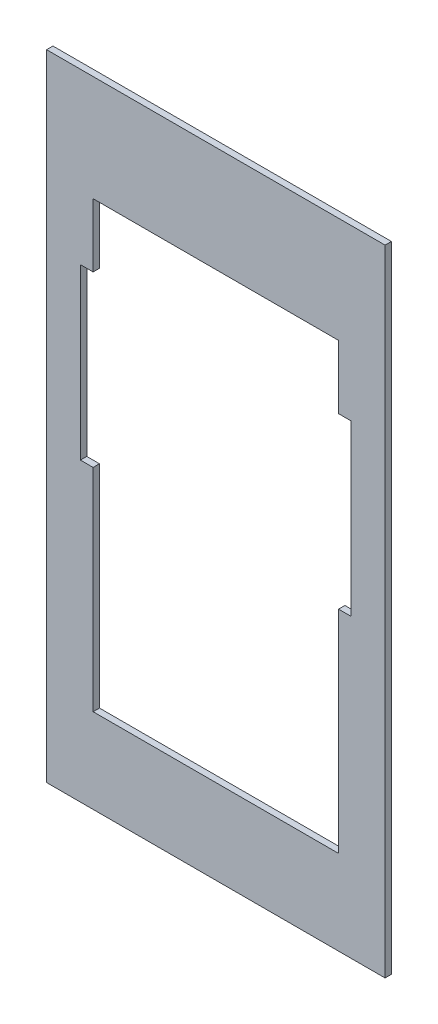
SolidWorks part; units mm, degrees
ref_plane "Front Plane" through (0, 0, 0) normal (0, 0, 1) x (1, 0, 0)
ref_plane "Top Plane" through (0, 0, 0) normal (0, 1, 0) x (1, 0, 0)
ref_plane "Right Plane" through (0, 0, 0) normal (1, 0, 0) x (0, 0, -1)
sketch "Sketch1" plane through (0, 0, 0) normal (0, 0, 1) x (1, 0, 0)
  line L1 (40, 75) -> (-40, 75)
  line L2 (40, 75) -> (40, -75)
  line L3 (40, -75) -> (-40, -75)
  line L4 (-40, 75) -> (-40, -75)
  line L5 (40, 75) -> (-40, -75) construction
  line L6 (40, -75) -> (-40, 75) construction
  line L20 (0, 0) -> (0, 75) construction
  line L21 (0, 0) -> (0, -75) construction
  line L23 (29, 50) -> (-29, 50)
  line L26 (-29, 50) -> (-29, 35)
  line L27 (-29, -55) -> (29, -55)
  line L33 (-29, 35) -> (-32, 35)
  line L35 (-29, -5) -> (-32, -5)
  line L36 (-32, 35) -> (-32, -5)
  line L37 (-29, -5) -> (-29, -55)
  line L38 (29, -5) -> (29, -55)
  line L39 (29, -5) -> (32, -5)
  line L40 (32, 35) -> (32, -5)
  line L41 (29, 35) -> (32, 35)
  line L42 (29, 50) -> (29, 35)
  point P0 (0, 0)
  dimension "D2" = 3
  dimension "D3" = 11
  dimension "D4" = 50
  dimension "D5" = 150
  dimension "D6" = 25
  dimension "D7" = 40
  dimension "D8" = 40
  dimension "D11" = 15
extrude "Boss-Extrude1" add sketch "Sketch1" along normal blind 1.5
